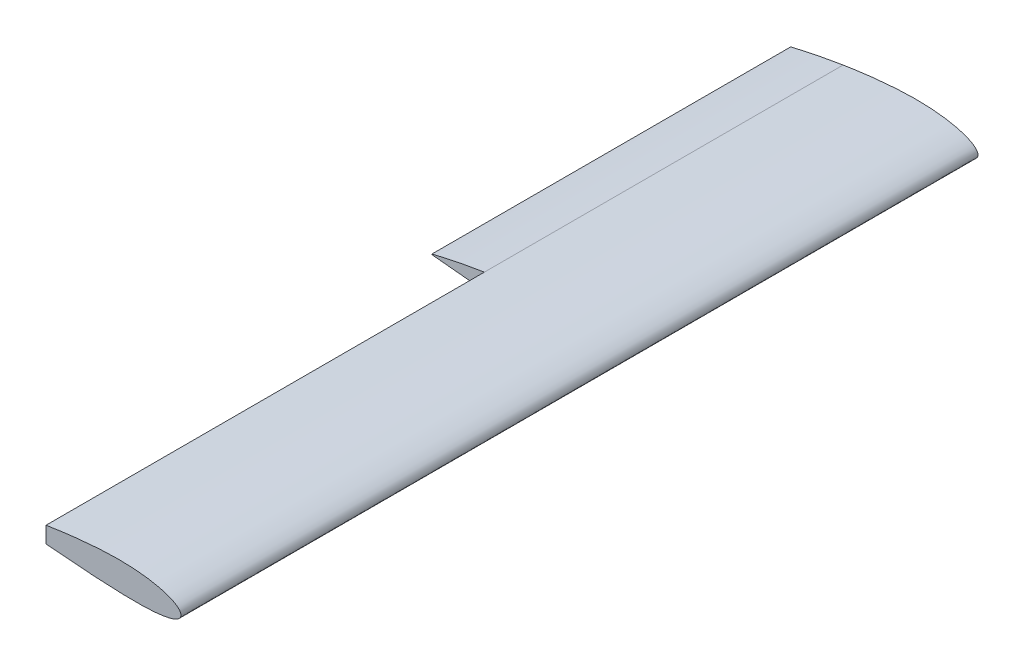
SolidWorks part; units mm, degrees
ref_plane "Front Plane" through (0, 0, 0) normal (0, 0, 1) x (1, 0, 0)
ref_plane "Top Plane" through (0, 0, 0) normal (0, 1, 0) x (1, 0, 0)
ref_plane "Right Plane" through (0, 0, 0) normal (1, 0, 0) x (0, 0, -1)
sketch "Sketch1" plane through (0, 0, 0) normal (0, 0, 1) x (1, 0, 0)
  line L0 (-189.5177, 15.2218) -> (-189.5177, -7.5941)
  spline S0 degree 3 poles (-189.5177, 15.2218) (-187.1369, 15.6014) (-181.5242, 16.4962) (-172.5795, 17.8022) (-162.6243, 19.1567) (-152.4681, 20.4133) (-142.1744, 21.5554) (-131.8072, 22.5613) (-121.4316, 23.4121) (-111.0981, 24.0888) (-100.8527, 24.5801) (-90.7586, 24.8093) (-80.8982, 24.774) (-71.3565, 24.4687) (-62.1976, 23.896) (-53.4829, 23.0627) (-45.2706, 21.981) (-37.6149, 20.6679) (-30.5654, 19.1446) (-24.1667, 17.4356) (-18.4578, 15.5683) (-13.4713, 13.5711) (-9.2335, 11.4718) (-5.7626, 9.2957) (-3.0694, 7.0598) (-1.1605, 4.7671) (-0.0625, 2.3959) (0.1432, -0.0144) (-0.535, -2.3343) (-2.0666, -4.442) (-4.3581, -6.3237) (-7.3821, -8.0146) (-11.1262, -9.5255) (-15.5729, -10.8568) (-20.6981, -12.0049) (-26.4717, -12.9669) (-32.8597, -13.7415) (-39.8243, -14.33) (-47.325, -14.7371) (-55.319, -14.9709) (-63.7608, -15.0426) (-72.6034, -14.9668) (-81.7972, -14.7606) (-91.2912, -14.4437) (-101.0512, -14.0339) (-111.0368, -13.559) (-121.1866, -12.9762) (-131.421, -12.31) (-141.6635, -11.5778) (-151.8521, -10.797) (-161.9248, -9.9836) (-171.82, -9.151) (-180.9981, -8.3559) (-186.8703, -7.8308) (-189.5177, -7.5941) knots 0 0 0 0 0.018424 0.043434 0.06908 0.095203 0.12164 0.148227 0.1748 0.201195 0.227364 0.253182 0.278347 0.30271 0.326128 0.348467 0.3696 0.389416 0.407811 0.424699 0.440008 0.453688 0.465715 0.476104 0.484928 0.49236 0.49873 0.504587 0.510443 0.516804 0.524199 0.532941 0.543186 0.554996 0.568376 0.583299 0.599709 0.617539 0.636704 0.657109 0.678651 0.701217 0.724685 0.748928 0.773811 0.799338 0.825326 0.851504 0.877716 0.9038 0.929596 0.954944 0.979688 1 1 1 1
extrude "Boss-Extrude1" add sketch "Sketch1" along normal blind 1120
sketch "Sketch2" plane through (0, 0, 0) normal (0, 0, 1) x (1, 0, 0)
  line L0 (-189.5177, 15.2218) -> (-189.5177, -7.5941)
  line L1 (-263.219, 0.4204) -> (-263.219, -0.4137)
  spline S0 degree 3 poles (-189.5177, 15.2218) (-190.2668, 15.1045) (-194.0251, 14.5158) (-200.6383, 13.3913) (-209.1995, 11.8813) (-217.2747, 10.3777) (-224.8169, 8.9107) (-231.7807, 7.4996) (-238.1249, 6.1663) (-243.8123, 4.9313) (-248.8094, 3.8144) (-253.0872, 2.8341) (-256.6212, 2.0071) (-259.3909, 1.3478) (-261.3806, 0.8681) (-262.5698, 0.579) (-263.0945, 0.4508) (-263.219, 0.4204) knots 0 0 0 0 0.030252 0.151774 0.267626 0.37709 0.479485 0.574175 0.66057 0.73813 0.806369 0.864859 0.913229 0.951173 0.978451 0.994887 1 1 1 1
  spline S1 degree 3 poles (-189.5177, -7.5941) (-189.9962, -7.5515) (-193.4821, -7.2417) (-199.8365, -6.6601) (-208.4252, -5.8654) (-216.5467, -5.0995) (-224.1497, -4.3713) (-231.1857, -3.6866) (-237.6098, -3.0518) (-243.3806, -2.4732) (-248.4606, -1.956) (-252.817, -1.5081) (-256.4209, -1.1292) (-259.2495, -0.8392) (-261.2822, -0.6051) (-262.5095, -0.5063) (-263.063, -0.4131) (-263.2098, -0.4136) (-263.219, -0.4137) knots 0 0 0 0 0.019463 0.141781 0.258505 0.3689 0.472262 0.567931 0.655294 0.733785 0.802892 0.862162 0.911205 0.949694 0.977373 0.994054 0.999628 1 1 1 1
extrude "Boss-Extrude2" add sketch "Sketch2" along normal blind 504
sketch "Sketch3" plane through (0, 0, 0) normal (0, 0, 1) x (1, 0, 0)
  circle A0 centre (-78.966, 4.935) radius 12.7
extrude "Cut-Extrude1" cut sketch "Sketch3" along normal blind 801
ref_plane "Plane1" through (0, 0, 330.7) normal (0, 0, 1) x (1, 0, 0)
sketch "Sketch4" plane through (0, 0, 330.7) normal (0, 0, 1) x (1, 0, 0)
  line L0 (-94.966, -15.812) -> (-62.966, -15.812)
  line L1 (-62.966, -15.812) -> (-62.966, 20.635)
  line L2 (-62.966, 20.635) -> (-94.966, 20.635)
  line L3 (-94.966, 20.635) -> (-94.966, -15.812)
extrude "Cut-Extrude2" cut sketch "Sketch4" along normal blind 46
ref_plane "Plane2" through (0, 0, 330.7) normal (0, 0, 1) x (1, 0, 0)
sketch "Sketch5" plane through (0, 0, 330.7) normal (0, 0, 1) x (1, 0, 0)
  line L0 (-240.5752, -7.706) -> (-180.5752, -7.706)
  line L1 (-180.5752, -7.706) -> (-180.5752, 4.294)
  line L2 (-180.5752, 4.294) -> (-240.5752, 4.294)
  line L3 (-240.5752, 4.294) -> (-240.5752, -7.706)
extrude "Cut-Extrude3" cut sketch "Sketch5" along normal blind 46
ref_plane "Plane3" through (0, 0, 534.5) normal (0, 0, 1) x (1, 0, 0)
sketch "Sketch6" plane through (0, 0, 534.5) normal (0, 0, 1) x (1, 0, 0)
  line L0 (-171.771, -14.359) -> (-117.771, -14.359)
  line L1 (-117.771, -14.359) -> (-117.771, 14.741)
  line L2 (-117.771, 14.741) -> (-171.771, 14.741)
  line L3 (-171.771, 14.741) -> (-171.771, -14.359)
extrude "Cut-Extrude4" cut sketch "Sketch6" along normal blind 64
ref_plane "Plane4" through (0, 0, -0.5) normal (0, 0, 1) x (1, 0, 0)
sketch "Sketch7" plane through (0, 0, -0.5) normal (0, 0, 1) x (1, 0, 0)
  line L0 (-194.454, 0.548) -> (-174.054, 0.548)
  line L1 (-174.054, 0.548) -> (-174.054, 7.348)
  line L2 (-174.054, 7.348) -> (-194.454, 7.348)
  line L3 (-194.454, 7.348) -> (-194.454, 0.548)
extrude "Cut-Extrude5" cut sketch "Sketch7" along normal blind 26
